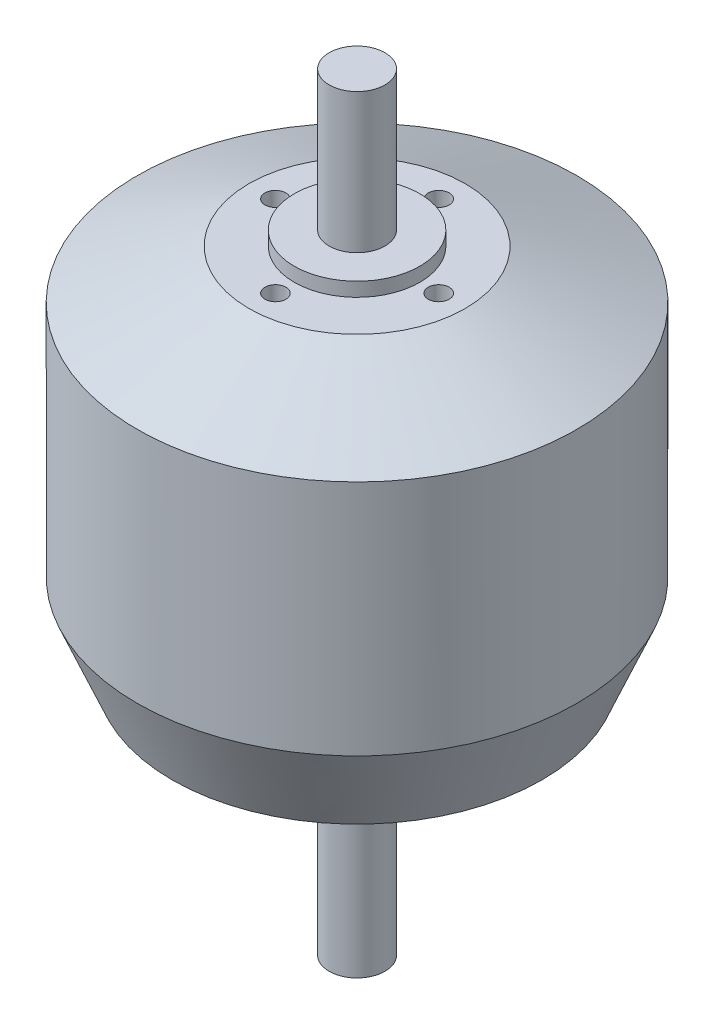
SolidWorks part; units mm, degrees
ref_plane "Front Plane" through (0, 0, 0) normal (0, 0, 1) x (1, 0, 0)
ref_plane "Top Plane" through (0, 0, 0) normal (0, 1, 0) x (1, 0, 0)
ref_plane "Right Plane" through (0, 0, 0) normal (1, 0, 0) x (0, 0, -1)
sketch "Sketch1" plane through (0, 0, 0) normal (0, 1, 0) x (1, 0, 0)
  line L0 (0, 0) -> (22.2, 0) construction
  circle A0 centre (0, 0) radius 4
  circle A1 centre (0, 0) radius 31.5
  circle A2 centre (0, 0) radius 9
  circle A3 centre (11.7, 0) radius 1.5
  circle A4 centre (22.2, 0) radius 2
  circle A5 centre (0, 11.7) radius 1.5
  circle A6 centre (0, 22.2) radius 2
  circle A7 centre (-11.7, 0) radius 1.5
  circle A8 centre (-22.2, 0) radius 2
  circle A9 centre (0, -11.7) radius 1.5
  circle A10 centre (0, -22.2) radius 2
  point P5 (11.7, 0)
  point P10 (-6.0935, 15.8932)
  point P11 (0, 0)
  point P25 (0, 0)
  dimension "D1" = 8
  dimension "D2" = 63
  dimension "D3" = 18
  dimension "D6" = 3
  dimension "D7" = 4
  dimension "D4" = 22.2
  dimension "D5" = 11.7
  dimension "D8" = 4
extrude "Boss-Extrude1" add sketch "Sketch1" along normal blind 55 contours A1 A2 | A2 A0 | A0 | A10 | A9 | L0 A3 | A4 | A5 | A6 | A7 | A8 | A3 L0 region at (-8.7454, 0, 0) region at (22.2, 0, -1.9434) region at (11.7, 0, -0.6366) region at (11.7, 0, 0.6366) region at (-3.8869, 0, 0) region at (-30.609, 0, 0) region at (0, 0, -11.7) region at (0, 0, -22.2) region at (-11.7, 0, 0) region at (-22.2, 0, 0) region at (0, 0, 11.7) region at (0, 0, 22.2)
extrude "Cut-Extrude1" cut sketch "Sketch1<4>" against normal blind 2 from surface contours A1 A2 | A10 | A8 | A7 | A9 | A5 | L0 A3 | A4 | A3 L0 | A6 region at (22.2, 0, -1.9434) region at (11.7, 0, -0.6366) region at (11.7, 0, 0.6366) region at (-30.609, 0, 0) region at (0, 0, -11.7) region at (0, 0, -22.2) region at (-11.7, 0, 0) region at (-22.2, 0, 0) region at (0, 0, 11.7) region at (0, 0, 22.2) starting at face at (0, 55, 31.5)
sketch "Sketch1<4>" plane through (0, 0, 0) normal (0, 1, 0) x (1, 0, 0) same geometry as "Sketch1"
extrude "Boss-Extrude2" add sketch "Sketch1<5>" against normal blind 35 contours A0 region at (0, 0, 0)
sketch "Sketch1<5>" plane through (0, 0, 0) normal (0, 1, 0) x (1, 0, 0) same geometry as "Sketch1"
extrude "Cut-Extrude2" cut sketch "Sketch1<7>" along normal blind 10 contours A10 | A8 | A6 | A4 region at (22.2, 0, 0) region at (0, 0, -22.2) region at (-22.2, 0, 0) region at (0, 0, 22.2)
sketch "Sketch1<7>" plane through (0, 0, 0) normal (0, 1, 0) x (1, 0, 0) same geometry as "Sketch1"
extrude "Cut-Extrude3" cut sketch "Sketch1<10>" against normal blind 5 from surface contours A7 | A5 | L0 A3 | A3 L0 | A9 region at (11.7, 0, -0.6366) region at (11.7, 0, 0.6366) region at (0, 0, -11.7) region at (-11.7, 0, 0) region at (0, 0, 11.7) starting at face at (0, 53, 9)
sketch "Sketch1<10>" plane through (0, 0, 0) normal (0, 1, 0) x (1, 0, 0) same geometry as "Sketch1"
chamfer "Chamfer1" distance 5 distance2 12 1 edges at (0, 0, 31.5) first distance on face at (0, 0, 24.2)
chamfer "Chamfer2" distance 7 distance2 16 1 edges at (0, 53, 31.5) first distance on face at (0, 12, 31.5)
extrude "Boss-Extrude4" add sketch "Sketch1<11>" along normal blind 20 from surface contours A0 region at (0, 0, 0) starting at face at (0, 55, 9)
sketch "Sketch1<11>" plane through (0, 0, 0) normal (0, 1, 0) x (1, 0, 0) same geometry as "Sketch1"
